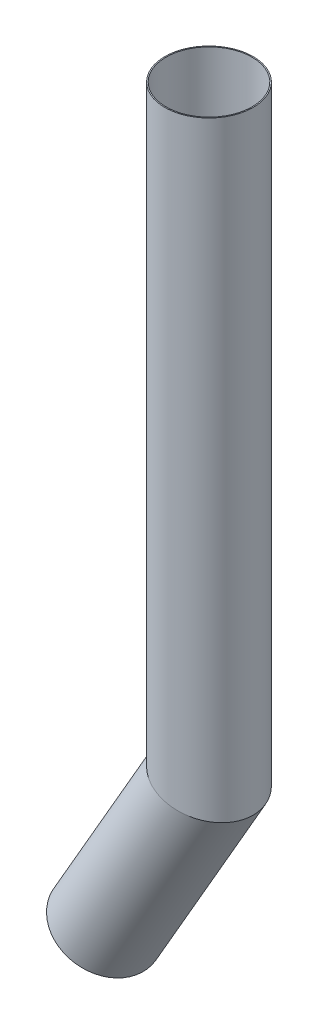
SolidWorks part; units mm, degrees
material "AISI 304"
ref_plane "Piano frontale" through (0, 0, 0) normal (0, 0, 1) x (1, 0, 0)
ref_plane "Piano superiore" through (0, 0, 0) normal (0, 1, 0) x (1, 0, 0)
ref_plane "Piano destro" through (0, 0, 0) normal (1, 0, 0) x (0, 0, -1)
sketch "Schizzo1" plane through (0, 0, 0) normal (0, 0, 1) x (1, 0, 0)
  line L0 (0, -62.6034) -> (0, 62.6034) construction
  line L1 (262.55, 454.7499) -> (404, 699.7485)
  line L4 (404, 699.7485) -> (404, 1516.7485)
  point P4 (0, 0)
  dimension "D1" = 30
sweep "Sweep1" add path "Schizzo1" circular profile diameter 120 parameters "D3"=120
shell "Svuota1" thickness 1.5 removed face at (262.55, 454.7499, -60) removed face at (404, 1516.7485, -60)
